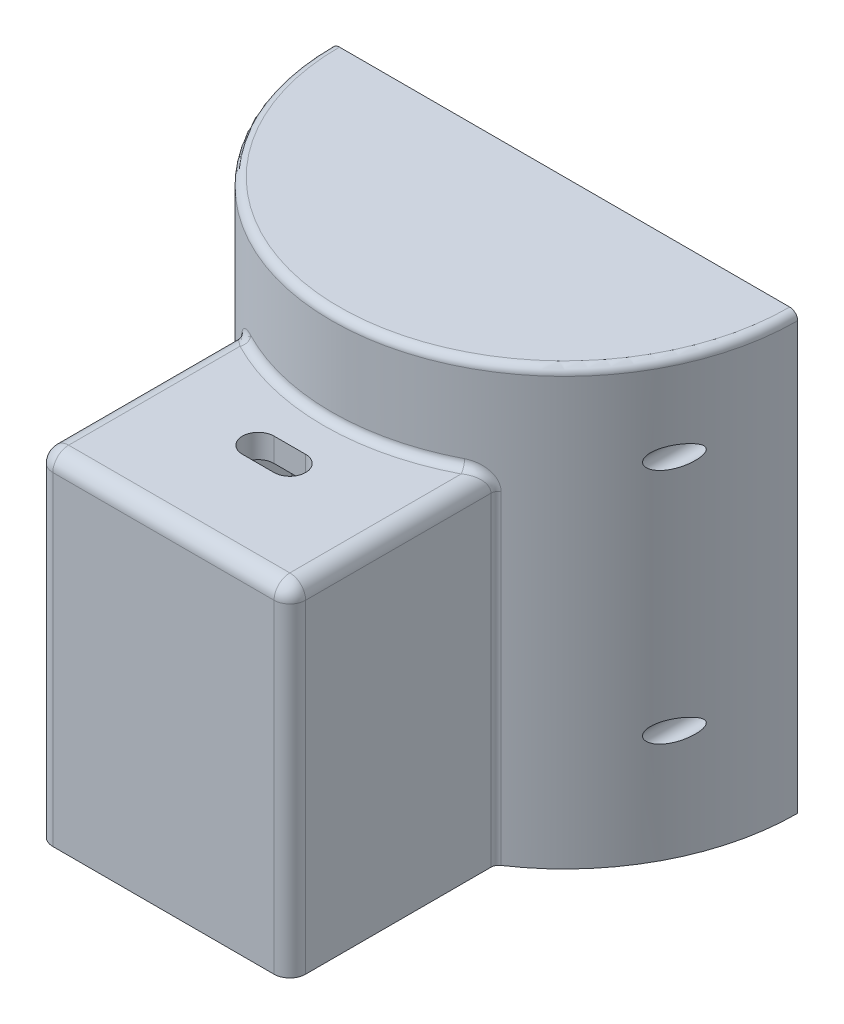
SolidWorks part; units mm, degrees
ref_plane "Спереди" through (0, 0, 0) normal (0, 0, 1) x (1, 0, 0)
ref_plane "Сверху" through (0, 0, 0) normal (0, 1, 0) x (1, 0, 0)
ref_plane "Справа" through (0, 0, 0) normal (1, 0, 0) x (0, 0, -1)
sketch "Эскиз1" plane through (0, 0, 0) normal (0, 1, 0) x (1, 0, 0)
  line L0 (-29.5, 0) -> (-26.5, 0)
  line L1 (26.5, 0) -> (29.5, 0)
  line L2 (-16, -24.7841) -> (-16, -50.7841)
  line L3 (-16, -50.7841) -> (16, -50.7841)
  line L4 (16, -50.7841) -> (16, -24.7841)
  line L5 (0, 0) -> (0, -50.7841) construction
  line L6 (-10, -24.5408) -> (-10, -44.7841)
  line L7 (-10, -44.7841) -> (10, -44.7841)
  line L8 (10, -44.7841) -> (10, -24.5408)
  arc A0 (29.5, 0) -> (16, -24.7841) centre (0, 0) cw
  arc A1 (26.5, 0) -> (10, -24.5408) centre (0, 0) cw
  arc A2 (-16, -24.7841) -> (-29.5, 0) centre (0, 0) cw
  arc A3 (-10, -24.5408) -> (-26.5, 0) centre (0, 0) cw
  point P17 (0, -44.7841)
  dimension "D1" = 29.5
  dimension "D2" = 26.5
  dimension "D3" = 32
  dimension "D4" = 20
  dimension "D5" = 20
  dimension "D6" = 6
extrude "Бобышка-Вытянуть1" add sketch "Эскиз1" along normal blind 43
sketch "Эскиз2" plane through (0, 43, 0) normal (0, 1, 0) x (1, 0, 0)
  line L0 (-29.5, 0) -> (-26.5, 0)
  line L1 (26.5, 0) -> (29.5, 0)
  arc A1 (26.5, 0) -> (-26.5, 0) centre (0, 0) cw
  arc A2 (-26.5, 0) -> (-10, -24.5408) centre (0, 0) ccw construction
  arc A3 (29.5, 0) -> (-29.5, 0) centre (0, 0) cw
  arc A4 (-29.5, 0) -> (-16, -24.7841) centre (0, 0) ccw construction
extrude "Бобышка-Вытянуть2" add sketch "Эскиз2" along normal blind 12
sketch "Эскиз4" plane through (0, 55, 0) normal (0, 1, 0) x (1, 0, 0)
  line L1 (-29.5, 0) -> (29.5, 0)
  arc A1 (29.5, 0) -> (-29.5, 0) centre (0, 0) cw
extrude "Бобышка-Вытянуть3" add sketch "Эскиз4" against normal blind 3 contours L1 A1
sketch "Эскиз6" plane through (0, 43, 0) normal (0, 1, 0) x (1, 0, 0)
  line L1 (10, -44.7841) -> (-10, -44.7841)
  line L2 (-10, -44.7841) -> (-10, -24.5408)
  line L3 (10, -24.5408) -> (10, -44.7841)
  arc A0 (-10, -24.5408) -> (10, -24.5408) centre (0, 0) ccw
extrude "Бобышка-Вытянуть4" add sketch "Эскиз6" against normal blind 3
fillet "Скругление2" radius 2 5 edges at (-16, 21.5, 50.7841) (16, 21.5, 50.7841) (-16, 43, 37.7841) (16, 43, 37.7841) (0, 43, 50.7841)
fillet "Скругление1" radius 1 11 edges at (-10, 40, 34.6624) (10, 40, 34.6624) (0, 55, 29.5) (10, 20, 44.7841) (-10, 20, 44.7841) (0, 40, 44.7841) (0, 43, 29.5) (-16, 20.5, 24.7841) (16, 20.5, 24.7841) (-15.6663, 42.1061, 24.9964) (15.4967, 42.3266, 25.1018)
sketch "Эскиз7" plane through (0, 43, 0) normal (0, 1, 0) x (1, 0, 0)
  line L0 (-2, -36.7841) -> (2, -36.7841) construction
  line L1 (-2, -34.7841) -> (2, -34.7841)
  line L2 (-2, -38.7841) -> (2, -38.7841)
  line L3 (-14, -48.7841) -> (14, -48.7841) construction
  arc A0 (-2, -34.7841) -> (-2, -38.7841) centre (-2, -36.7841) ccw
  arc A1 (2, -38.7841) -> (2, -34.7841) centre (2, -36.7841) ccw
  point P2 (0, -36.7841)
  dimension "D2" = 2
  dimension "D1" = 4
  dimension "D3" = 12
extrude "Вырез-Вытянуть1" cut sketch "Эскиз7" against normal up to surface (3 mm away) up to face at (0, 40, 34.7483)
hole_wizard "Сверло под метчик  спиральное M2.52" positions "Эскиз9" profile "Эскиз11" hole size "M2.5x0.45" standard "Ansi Metric"
sketch "Эскиз9" plane through (0, 0, 0) normal (0, -1, 0) x (-1, 0, 0)
  point P0 (13, -36)
  point P2 (0, -48)
  point P4 (-13, -36)
  point P7 (0, 0)
  point P9 (0, -54.332)
  point P10 (0, -47.9664)
  point P11 (0, 0)
  point P12 (0, 0)
  dimension "D1" = 36
  dimension "D2" = 12
  dimension "D3" = 13
  dimension "D4" = 26
sketch "Эскиз11" plane through (-13, 0, 36) normal (1, 0, 0) x (0, 0, -1)
  line L0 (0, 0) -> (0, 5.7661)
  line L1 (0, 5.7661) -> (1.275, 5)
  line L2 (1.275, 5) -> (1.275, 0)
  line L5 (1.275, 0) -> (0, 0)
  line L10 (0, 5.7661) -> (-1.275, 5) construction
  line L11 (0, -6.35) -> (0, 107.95) construction
  dimension "Диаметр отверстия" = 2.55
  dimension "Глубина отверстия" = 5
  dimension "Угол заточки сверла" = 118
sketch "Эскиз12" plane through (0, 0, 0) normal (0, 0, -1) x (-1, 0, 0)
  line L0 (-26.5, 52) -> (-26.5, 0) construction
  line L1 (-26.5, 14) -> (26.5, 14) construction
  line L2 (-26.5, 14) -> (-26.5, 44) construction
  line L3 (-26.5, 44) -> (26.5, 44) construction
  line L4 (26.5, 14) -> (26.5, 44) construction
  line L5 (26.5, 52) -> (26.5, 0) construction
  circle A0 centre (-26.5, 44) radius 3
  circle A1 centre (26.5, 44) radius 3
  circle A2 centre (26.5, 14) radius 3
  circle A3 centre (-26.5, 14) radius 3
  point P8 (26.5, 29)
  dimension "D3" = 6
  dimension "D1" = 30
  dimension "D2" = 29
extrude "Бобышка-Вытянуть5" add sketch "Эскиз12" against normal up to surface (12.2474 mm away) up to face at (0.0149, 26.2344, 18.095)
sketch "Эскиз16" plane through (0, 0, 0) normal (0, 0, -1) x (-1, 0, 0)
  circle A0 centre (-26.5, 44) radius 1.3
  circle A1 centre (26.5, 44) radius 1.3
  circle A2 centre (26.5, 14) radius 1.3
  circle A3 centre (-26.5, 14) radius 1.3
  dimension "D1" = 2.6
extrude "Вырез-Вытянуть2" cut sketch "Эскиз16" against normal through all
